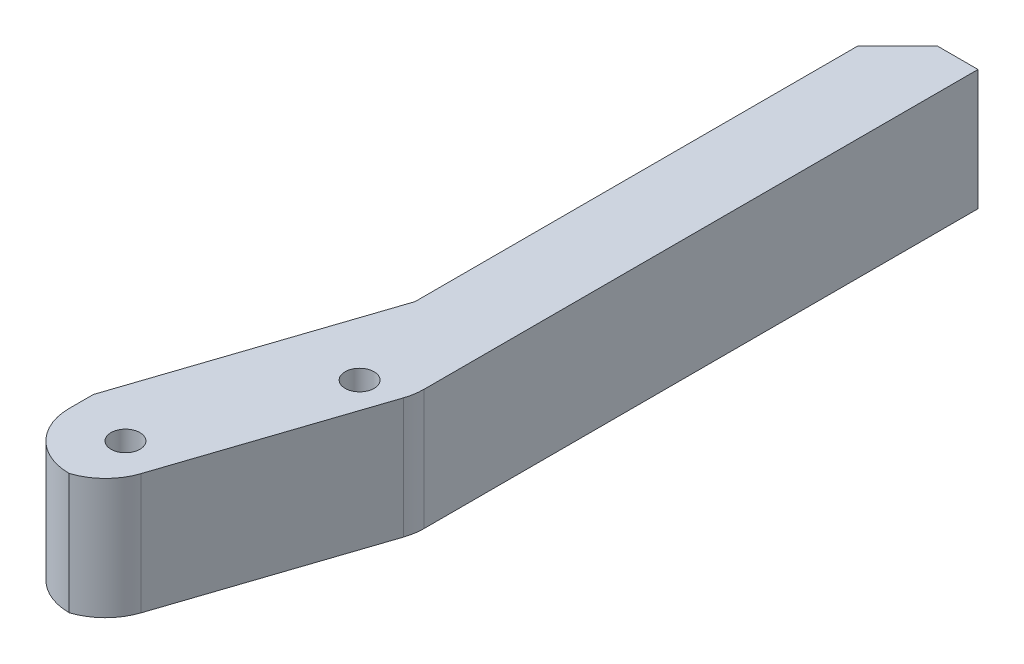
SolidWorks part; units mm, degrees
ref_plane "Front Plane" through (0, 0, 0) normal (0, 0, 1) x (1, 0, 0)
ref_plane "Top Plane" through (0, 0, 0) normal (0, 1, 0) x (1, 0, 0)
ref_plane "Right Plane" through (0, 0, 0) normal (1, 0, 0) x (0, 0, -1)
sketch "Sketch1" plane through (0, 0, 0) normal (0, 1, 0) x (1, 0, 0)
  line L2 (10.929, 60.2914) -> (10.929, 0.2914)
  line L4 (20.929, -9.7086) -> (10.929, -39.7086)
  line L5 (10.929, -39.7086) -> (0.929, -39.7086)
  line L6 (0.929, -39.7086) -> (0.929, -29.7086)
  line L7 (20.929, -9.7086) -> (20.929, -39.7086) construction
  line L8 (20.929, -39.7086) -> (10.929, -39.7086) construction
  line L9 (20.929, -9.7086) -> (20.929, 60.2914)
  line L10 (20.929, 60.2914) -> (10.929, 60.2914)
  line L12 (10.929, 0.2914) -> (0.929, -29.7086)
  dimension "D1" = 70
  dimension "D2" = 10
  dimension "D3" = 30
  dimension "D4" = 10
  dimension "D5" = 10
  dimension "D6" = 10
  dimension "D7" = 12.6491
extrude "Boss-Extrude1" add sketch "Sketch1" along normal blind 15
fillet "Fillet1" radius 7 1 edges at (0.929, 7.5, 39.7086)
sketch "Sketch2" plane through (0, 15, 0) normal (0, 1, 0) x (1, 0, 0)
  line L1 (0.929, -29.7086) -> (0.929, -32.7086) construction
  circle A0 centre (15.929, -11.5992) radius 1.8
  circle A1 centre (7.929, -32.7086) radius 1.8
  dimension "D1" = 3.6
  dimension "D2" = 15
extrude "Cut-Extrude1" cut sketch "Sketch2" against normal through all
fillet "Fillet3" radius 7 1 edges at (10.929, 7.5, 39.7086)
fillet "Fillet5" radius 7 1 edges at (20.929, 7.5, 9.7086)
chamfer "Chamfer2" distance 5 angle 45 1 edges at (10.929, 7.5, -60.2914)
